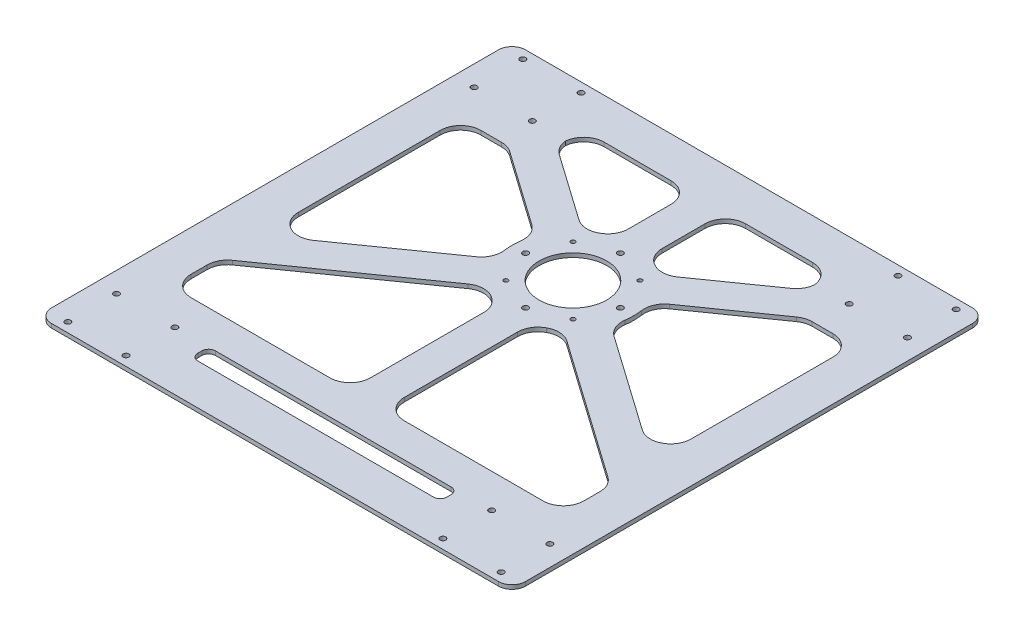
SolidWorks part; units mm, degrees
ref_plane "Front Plane" through (0, 0, 0) normal (0, 0, 1) x (1, 0, 0)
ref_plane "Top Plane" through (0, 0, 0) normal (0, 1, 0) x (1, 0, 0)
ref_plane "Right Plane" through (0, 0, 0) normal (1, 0, 0) x (0, 0, -1)
sketch "Sketch1" plane through (0, 0, 0) normal (0, 1, 0) x (1, 0, 0)
  line L1 (0, 0) -> (350, 0)
  line L2 (0, 0) -> (0, 350)
  line L3 (0, 350) -> (350, 350)
  line L4 (350, 0) -> (350, 350)
  dimension "D1" = 350
  dimension "D2" = 350
extrude "Boss-Extrude1" add sketch "Sketch1" along normal blind 3
fillet "Fillet1" radius 10 4 edges at (0, 1.5, -350) (350, 1.5, -350) (350, 1.5, 0) (0, 1.5, 0)
sketch "Sketch2" plane through (0, 3, 0) normal (0, 1, 0) x (1, 0, 0)
  line L0 (15, 343) -> (58, 343) construction
  line L1 (58, 343) -> (58, 307) construction
  line L2 (58, 307) -> (15, 307) construction
  line L3 (15, 307) -> (15, 343) construction
  line L4 (340, 350) -> (10, 350) construction
  line L5 (0, 340) -> (0, 10) construction
  line L6 (0, 175) -> (350, 175) construction
  line L7 (350, 10) -> (350, 340) construction
  line L8 (175, 350) -> (175, 0) construction
  line L9 (10, 0) -> (340, 0) construction
  circle A0 centre (15, 343) radius 2.1
  circle A1 centre (58, 343) radius 2.1
  circle A2 centre (58, 307) radius 2.1
  circle A3 centre (15, 307) radius 2.1
  circle A4 centre (58, 43) radius 2.1 construction
  circle A5 centre (15, 43) radius 2.1 construction
  circle A6 centre (58, 7) radius 2.1
  circle A7 centre (15, 7) radius 2.1
  circle A8 centre (292, 43) radius 2.1 construction
  circle A9 centre (292, 7) radius 2.1
  circle A10 centre (335, 7) radius 2.1
  circle A11 centre (335, 43) radius 2.1 construction
  circle A12 centre (335, 307) radius 2.1 construction
  circle A13 centre (292, 307) radius 2.1 construction
  circle A14 centre (292, 343) radius 2.1
  circle A15 centre (335, 343) radius 2.1
  circle A36 centre (292, 307) radius 2.1
  circle A37 centre (335, 307) radius 2.1
  circle A52 centre (15, 43) radius 2.1
  circle A53 centre (58, 43) radius 2.1
  circle A68 centre (292, 43) radius 2.1
  circle A69 centre (335, 43) radius 2.1
  circle A128 centre (15, 289) radius 2.1 [skipped]
  circle A129 centre (58, 289) radius 2.1 [skipped]
  circle A150 centre (58, 325) radius 2.1 [skipped]
  circle A151 centre (15, 325) radius 2.1 [skipped]
  point P44 (0, 0)
  point P45 (0, 0)
  dimension "D1" = 4.2
  dimension "D2" = 7
  dimension "D3" = 15
  dimension "D4" = 43
  dimension "D5" = 36
  dimension "D6" = 2
extrude "Cut-Extrude1" cut sketch "Sketch2" against normal through all
sketch "Sketch3" plane through (0, 3, 0) normal (0, 1, 0) x (1, 0, 0)
  line L0 (175, 350) -> (175, 0) construction
  line L9 (340, 350) -> (10, 350) construction
  line L10 (10, 0) -> (340, 0) construction
  line L11 (0, 175) -> (350, 175) construction
  line L12 (0, 340) -> (0, 10) construction
  line L13 (350, 10) -> (350, 340) construction
  line L14 (83, 300) -> (320, 133.2832)
  line L15 (30, 282) -> (320, 282)
  line L16 (30, 282) -> (30, 68)
  line L17 (30, 68) -> (320, 68)
  line L18 (320, 282) -> (320, 68)
  line L19 (83, 320) -> (267, 320)
  line L20 (83, 320) -> (83, 30)
  line L21 (83, 30) -> (267, 30)
  line L22 (267, 320) -> (267, 30)
  line L27 (65.1367, 282) -> (320, 102.7173)
  line L28 (267, 300) -> (30, 133.2832)
  line L29 (284.8633, 282) -> (30, 102.7173)
  line L30 (153.2742, 220) -> (196.7258, 220) construction
  line L32 (162.5, 320) -> (187.5, 320)
  line L33 (162.5, 320) -> (162.5, 30)
  line L34 (162.5, 30) -> (187.5, 30)
  line L35 (187.5, 320) -> (187.5, 30)
  circle A0 centre (292, 43) radius 2.1 construction
  circle A1 centre (292, 307) radius 2.1 construction
  circle A2 centre (175, 220) radius 25
  circle A3 centre (175, 220) radius 45
  point P4 (30, 175)
  point P5 (175, 282)
  point P22 (83, 175)
  point P27 (175, 320)
  point P31 (175, 320)
  dimension "D5" = 50
  dimension "D6" = 90
  dimension "D1" = 30
  dimension "D2" = 30
  dimension "D3" = 25
  dimension "D4" = 25
  dimension "D7" = 100
  dimension "D8" = 25
  dimension "D9" = 20
  dimension "D10" = 25
extrude "Cut-Extrude2" cut sketch "Sketch3" against normal blind 10 contours A3 L14 L22 L29 | L15 L29 L22 L14 L18 | L27 L22 L17 L18 | L20 L29 L16 L17 | L28 L20 L27 L15 L16 | A3 L27 L20 L28 | L29 A2 L27 | L28 A2 L14 | L14 A2 L33 L28 | L33 A2 L27 L28 | L28 A2 L33 L27 | L35 L14 L28 L33 L27 L29 | L14 L35 L29 | L29 A2 L35 L14 | L35 A2 L28 L14 | L35 A2 L14 L29 | L27 A2 L35 L29 | L33 A2 L29 L27 | L33 L28 L27 | L27 A2 L28 | L14 A2 L29 | A3 L29 L20 L17 L33 | A3 L35 L17 L22 L27 | L19 L35 L15 L28 L22 | L33 L19 L20 L14 L15 | A3 L33 L15 L14 | A3 L28 L15 L35 region at (125.3264, 3, -302.0728) region at (142.1913, 3, -272.1267) region at (54.8731, 3, -215.5026) region at (102.8163, 3, -220) region at (224.6736, 3, -302.0728) region at (207.8087, 3, -272.1267) region at (175, 3, -241.2231) region at (166.744, 3, -235.1171) region at (157.1328, 3, -229.855) region at (151.1138, 3, -220) region at (125.8254, 3, -117.9208) region at (59.586, 3, -95.7648) region at (183.256, 3, -235.1171) region at (175, 3, -220) region at (159.4247, 3, -220) region at (157.1328, 3, -210.145) region at (192.8672, 3, -229.855) region at (190.5753, 3, -220) region at (166.744, 3, -204.8829) region at (247.1837, 3, -220) region at (295.1269, 3, -215.5026) region at (198.8862, 3, -220) region at (192.8672, 3, -210.145) region at (183.256, 3, -204.8829) region at (175, 3, -198.7769) region at (224.1746, 3, -117.9208) region at (290.414, 3, -95.7648)
fillet "Fillet2" radius 15 30 edges at (146.8346, 1.5, -184.9042) (162.5, 1.5, -176.771) (30, 1.5, -102.7173) (30, 1.5, -68) (203.1654, 1.5, -184.9042) (187.5, 1.5, -176.771) (320, 1.5, -102.7173) (320, 1.5, -68) (284.8633, 1.5, -282) (320, 1.5, -282) (320, 1.5, -133.2832) (217.5492, 1.5, -234.6481) (217.5492, 1.5, -205.3519) (187.5, 1.5, -263.229) (203.1654, 1.5, -255.0958) (267, 1.5, -300) (267, 1.5, -320) (162.5, 1.5, -320) (146.8346, 1.5, -255.0958) (162.5, 1.5, -263.229) (83, 1.5, -300) (187.5, 1.5, -320) (83, 1.5, -320) (30, 1.5, -133.2832) (132.4508, 1.5, -205.3519) (132.4508, 1.5, -234.6481) (65.1367, 1.5, -282) (30, 1.5, -282) (187.5, 1.5, -68) (162.5, 1.5, -68)
sketch "Sketch4" plane through (0, 3, 0) normal (0, 1, 0) x (1, 0, 0)
  line L0 (10, 0) -> (340, 0) construction
  line L1 (83, 43) -> (267, 43)
  line L2 (83, 43) -> (83, 30)
  line L3 (83, 30) -> (267, 30)
  line L4 (267, 43) -> (267, 30)
  line L5 (202.5, 68) -> (305, 68) construction
  line L7 (175, 0) -> (175, 30) construction
  circle A0 centre (58, 43) radius 2.1 construction
  dimension "D3" = 25
  dimension "D1" = 30
  dimension "D2" = 25
extrude "Cut-Extrude3" cut sketch "Sketch4" against normal blind 10
fillet "Fillet4" radius 5 4 edges at (267, 1.5, -30) (267, 1.5, -43) (83, 1.5, -30) (83, 1.5, -43)
sketch "Sketch5" plane through (0, 3, 0) normal (0, 1, 0) x (1, 0, 0)
  line L0 (175, 255) -> (175, 220) construction
  line L2 (199.7487, 244.7487) -> (175, 220) construction
  circle A0 centre (175, 220) radius 35 construction
  circle A1 centre (175, 255) radius 2.1
  circle A2 centre (210, 220) radius 2.1
  circle A3 centre (175, 185) radius 2.1
  circle A4 centre (140, 220) radius 2.1
  circle A9 centre (199.7487, 244.7487) radius 1.6
  circle A10 centre (199.7487, 195.2513) radius 1.6
  circle A11 centre (150.2513, 195.2513) radius 1.6
  circle A12 centre (150.2513, 244.7487) radius 1.6
  point P7 (175, 220)
  point P22 (175, 220)
  point P23 (175, 220)
  point P39 (175, 220)
  dimension "D1" = 70
  dimension "D2" = 4.2
  dimension "D4" = 4
  dimension "3.2" = 3.2
  dimension "D5" = 45
  dimension "D3" = 4
extrude "Cut-Extrude4" cut sketch "Sketch5" against normal blind 10
